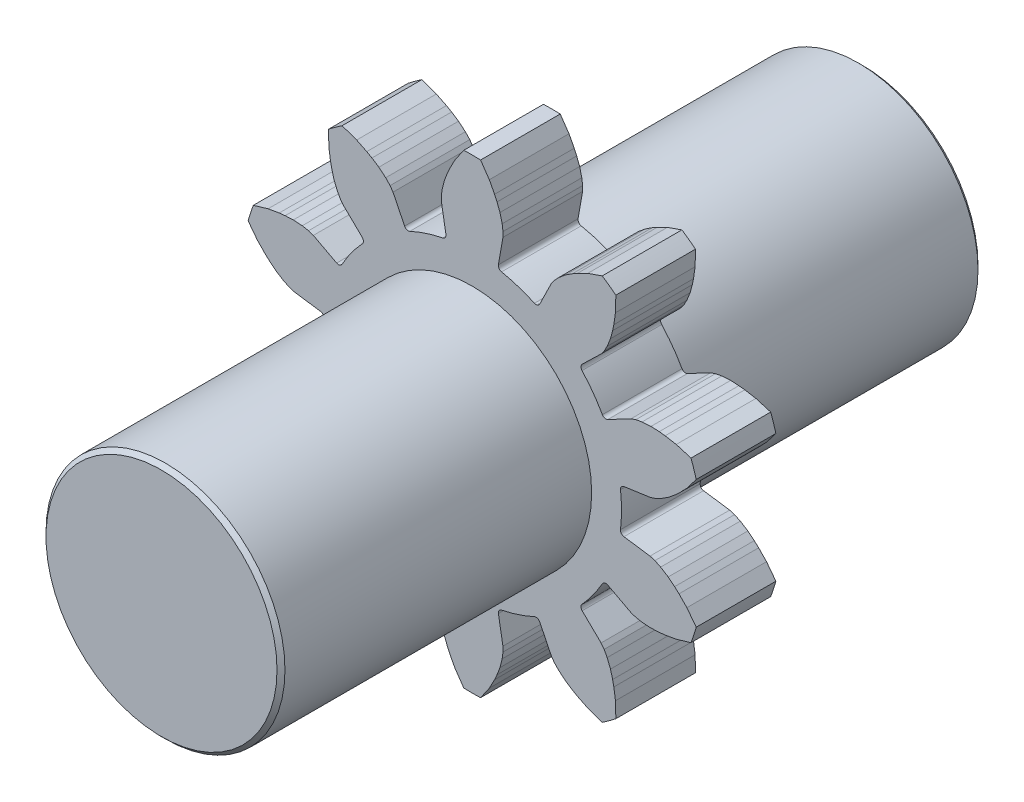
SolidWorks part; units mm, degrees
material "PW70:3:C1:0:1:2:Re:26:"
ref_plane "Plan1" through (0, 0, 0) normal (0, 0, 1) x (1, 0, 0)
ref_plane "Plan2" through (0, 0, 0) normal (0, 1, 0) x (1, 0, 0)
ref_plane "Plan3" through (0, 0, 0) normal (1, 0, 0) x (0, 0, -1)
sketch "Esquisse1" plane through (0, 0, 0) normal (0, 0, 1) x (1, 0, 0)
  circle A0 centre (0, 0) radius 29.25
  dimension "D1" = 58.5
extrude "Base-Extrusion" add sketch "Esquisse1" along normal blind 10
sketch "Esquisse2" plane through (0, 0, 10) normal (0, 0, 1) x (1, 0, 0)
  line L0 (1.0549, 29.231) -> (2.154, 27.6377)
  line L1 (2.154, 27.6377) -> (2.8137, 26.3859)
  line L2 (2.9743, 26.0813) -> (2.154, 27.6377) construction
  line L3 (2.8137, 26.3859) -> (3.119, 25.7041)
  line L4 (3.4898, 24.7374) -> (2.9743, 26.0813) construction
  line L5 (3.119, 25.7041) -> (3.4898, 24.7374)
  line L6 (3.4898, 24.7374) -> (3.6272, 24.1947)
  line L7 (3.7645, 23.652) -> (3.4898, 24.7374) construction
  line L8 (3.6272, 24.1947) -> (3.7645, 23.652)
  line L9 (3.7645, 23.652) -> (3.868, 22.859)
  line L10 (3.868, 22.859) -> (3.8596, 22.2199)
  line L11 (3.8596, 22.2199) -> (3.7076, 21.3447)
  line L12 (3.8596, 22.2199) -> (3.1815, 18.3161) construction
  line L13 (3.7076, 21.3447) -> (3.2933, 18.9596)
  line L14 (0, 0) -> (0, 30) construction
  line L15 (0, 0) -> (9.631, 29.6412) construction
  line L16 (9.5466, 19.4474) -> (8.4799, 17.2744)
  line L17 (9.9381, 20.2449) -> (9.5466, 19.4474)
  line L18 (10.3069, 20.7669) -> (9.9381, 20.2449)
  line L19 (10.8568, 21.3475) -> (10.3069, 20.7669)
  line L20 (11.2868, 21.7059) -> (10.8568, 21.3475)
  line L21 (11.7169, 22.0642) -> (11.2868, 21.7059)
  line L22 (12.5852, 22.6283) -> (11.7169, 22.0642)
  line L23 (13.2329, 23.0005) -> (12.5852, 22.6283)
  line L24 (14.5025, 23.6255) -> (13.2329, 23.0005)
  line L25 (16.3281, 24.2684) -> (14.5025, 23.6255)
  arc A0 (16.3281, 24.2684) -> (1.0549, 29.231) centre (0, 0) ccw
  arc A1 (7.8224, 17.0403) -> (3.6876, 18.3838) centre (0, 0) ccw
  arc A2 (3.6876, 18.3838) -> (3.2933, 18.9596) centre (3.7859, 18.874) cw
  arc A3 (7.8224, 17.0403) -> (8.4799, 17.2744) centre (8.031, 17.4947) ccw
  dimension "D1" = 37.5
  dimension "D3" = 0.5
  dimension "D2" = 18
extrude "Enlèv. mat.-Extru.1" cut sketch "Esquisse2" against normal through all
ref_axis "Axe1" through (0, 0, -50) along (0, 0, 1)
ref_axis "Axe3" through (0, 50, 0) along (0, -1, 0)
pattern_circular "Répétition circulaire1" count 10 over 360 about axis through (0, 0, -50) along (0, 0, 1) of "Enlèv. mat.-Extru.1"
sketch "Esquisse3" plane through (0, 0, 10) normal (0, 0, 1) x (1, 0, 0)
  circle A0 centre (0, 0) radius 15
  dimension "D1" = 30
extrude "Boss.-Extru.1" add sketch "Esquisse3" along normal blind 39 and the other way blind 49
chamfer "Chanfrein1" distance 0.5 angle 45 2 edges at (15, 0, -39) (15, 0, 49)
